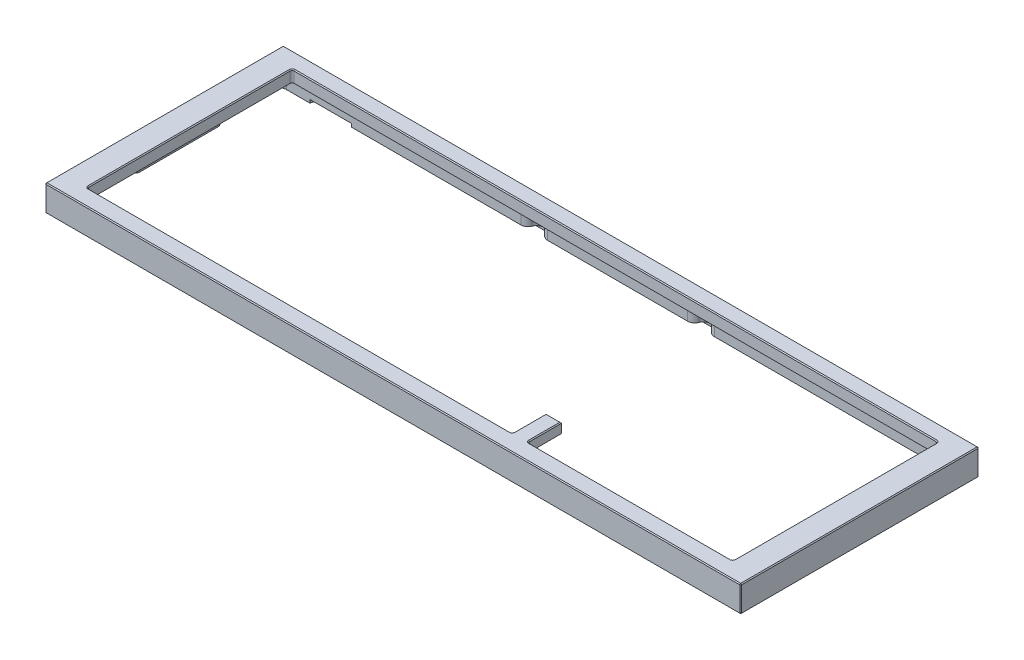
SolidWorks part; units mm, degrees
material "6061 Alloy"
ref_plane "Front Plane" through (0, 0, 0) normal (0, 0, 1) x (1, 0, 0)
ref_plane "Top Plane" through (0, 0, 0) normal (0, 1, 0) x (1, 0, 0)
ref_plane "Right Plane" through (0, 0, 0) normal (1, 0, 0) x (0, 0, -1)
sketch "Sketch1" plane through (0, 0, 0) normal (0, 1, 0) x (1, 0, 0)
  line L1 (0, 0) -> (390.8, 0)
  line L2 (0, 0) -> (0, -133.8)
  line L3 (0, -133.8) -> (390.8, -133.8)
  line L4 (390.8, 0) -> (390.8, -133.8)
  dimension "D1" = 390.8
  dimension "D2" = 133.8
extrude "Boss-Extrude1" add sketch "Sketch1" along normal blind 13.1
sketch "Sketch2" plane through (0, 13.1, 0) normal (0, 1, 0) x (1, 0, 0)
  line L0 (390.8, 0) -> (0, 0) construction
  line L1 (14, -9) -> (376.8, -9)
  line L2 (14, -9) -> (14, -124.3)
  line L3 (14, -124.3) -> (376.8, -124.3)
  line L4 (376.8, -9) -> (376.8, -124.3)
  line L5 (0, -133.8) -> (390.8, -133.8) construction
  line L6 (0, 0) -> (0, -133.8) construction
  line L7 (390.8, -133.8) -> (390.8, 0) construction
  line L8 (390.8, -133.8) -> (390.8, 0) construction
  line L9 (261.6, -124.3) -> (252.9, -124.3)
  line L10 (261.6, -124.3) -> (261.6, -105.25)
  line L11 (261.6, -105.25) -> (252.9, -105.25)
  line L12 (252.9, -124.3) -> (252.9, -105.25)
  line L13 (0, -133.8) -> (390.8, -133.8) construction
  dimension "D1" = 9
  dimension "D2" = 9.5
  dimension "D3" = 14
  dimension "D4" = 14
  dimension "D5" = 129.2
  dimension "D6" = 137.9
  dimension "D7" = 28.55
extrude "Cut-Extrude1" cut sketch "Sketch2" against normal through all contours L3 L12 L11 L10 L4 L1 L2 region at (195.154, 13.1, 66.4586)
sketch "Sketch3" plane through (0, 0, 0) normal (0, -1, 0) x (1, 0, 0)
  line L0 (390.8, 0) -> (0, 0) construction
  line L1 (385.5, 2.6) -> (5.3, 2.6)
  line L2 (385.5, 2.6) -> (385.5, 131.2)
  line L3 (385.5, 131.2) -> (5.3, 131.2)
  line L4 (5.3, 2.6) -> (5.3, 131.2)
  line L5 (390.8, 133.8) -> (390.8, 0) construction
  point P4 (195.4, 2.6)
  point P7 (195.4, 0)
  point P8 (385.5, 66.9)
  point P11 (390.8, 66.9)
  dimension "D1" = 380.2
  dimension "D2" = 128.6
extrude "Cut-Extrude2" cut sketch "Sketch3" against normal blind 6.6 contours L2 L1 L4 L3
sketch "Sketch5" plane through (0, 6.6, 0) normal (0, -1, 0) x (1, 0, 0)
  line L0 (290, 128.2) -> (285, 128.2)
  line L1 (290, 128.2) -> (290, 131.2)
  line L2 (290, 131.2) -> (285, 131.2)
  line L3 (285, 128.2) -> (285, 131.2)
  line L4 (105, 128.2) -> (100, 128.2)
  line L5 (105, 128.2) -> (105, 131.2)
  line L6 (105, 131.2) -> (100, 131.2)
  line L7 (100, 128.2) -> (100, 131.2)
  line L8 (8.3, 45) -> (8.3, 88.8)
  line L9 (382.5, 45) -> (382.5, 88.8)
  line L10 (0, 133.8) -> (390.8, 133.8) construction
  line L11 (5.3, 2.6) -> (5.3, 131.2) construction
  line L12 (390.8, 0) -> (0, 0) construction
  line L13 (385.5, 2.6) -> (385.5, 131.2) construction
  line L15 (385.5, 131.2) -> (5.3, 131.2) construction
  line L16 (385.5, 131.2) -> (5.3, 131.2) construction
  line L17 (385.5, 2.6) -> (5.3, 2.6) construction
  line L18 (5.3, 2.6) -> (5.3, 131.2) construction
  circle A0 centre (102.5, 128.2) radius 2.5
  circle A1 centre (287.5, 128.2) radius 2.5
  circle A2 centre (102.5, 2.6) radius 2.5
  circle A3 centre (195.4, 2.6) radius 2.5
  circle A4 centre (287.5, 2.6) radius 2.5
  circle A5 centre (385.5, 45) radius 3
  circle A6 centre (385.5, 88.8) radius 3
  circle A7 centre (5.3, 45) radius 3
  circle A8 centre (5.3, 88.8) radius 3
  line M9 (5.3, 131.2) -> (5.3, 2.6)
  line M10 (5.3, 2.6) -> (385.5, 2.6)
  line M11 (385.5, 2.6) -> (385.5, 131.2)
  dimension "D1" = 5
  dimension "D5" = 6
  dimension "D2" = 185
  dimension "D3" = 92.9
  dimension "D4" = 185
  dimension "D6" = 45
  dimension "D7" = 97.2
  dimension "D8" = 3
  dimension "D9" = 97.2
  dimension "D10" = 45
  dimension "D11" = 45
extrude "Boss-Extrude2" add sketch "Sketch5" along normal up to surface (6.6 mm away) contours A6 L9 A5 M11 | A5 M11 | A6 M11 | A4 M10 | A3 M10 | A2 M10 | A7 M9 | A8 A7 L8 M9 | A8 M9 | A0 | L7 L6 L5 L4 | L3 L2 L1 L0 | A1 region at (6.8273, 6.6, 66.9) region at (6.5732, 6.6, 45) region at (384.2268, 6.6, 45) region at (287.5, 6.6, 3.661) region at (195.4, 6.6, 3.661) region at (102.5, 6.6, 3.661) region at (6.5732, 6.6, 88.8) region at (383.9727, 6.6, 66.9) region at (384.2268, 6.6, 88.8) up to face at (195.4, 0, 66.9)
sketch "Sketch6" plane through (0, 6.6, 0) normal (0, -1, 0) x (-1, 0, 0)
  line L0 (-195.4, 0) -> (-195.4, -133.8) construction
  line L1 (-390.8, 0) -> (0, 0) construction
  line L2 (0, -133.8) -> (-390.8, -133.8) construction
  line L3 (-390.8, -66.9) -> (0, -66.9) construction
  line L4 (-390.8, -133.8) -> (-390.8, 0) construction
  line L5 (0, 0) -> (0, -133.8) construction
  line L6 (-285, -2.6) -> (-197.9, -2.6) construction
  line L7 (-385.5, -2.6) -> (-385.5, -42) construction
  line L8 (-385.5, -2.6) -> (-385.5, -42) construction
  point P12 (-382.9, -22.7)
  point P13 (-382.9, -111)
  point P14 (-324.8, -129)
  point P15 (-192.2, -129)
  point P16 (-148.6, -5.4)
  point P18 (-64.4, -129)
  point P19 (-7.9, -111)
  point P20 (-7.9, -22.7)
  point P22 (-242.3, -5.4)
  dimension "D1" = 22.8
  dimension "D2" = 22.7
  dimension "D3" = 7.9
  dimension "D4" = 66
  dimension "D5" = 4.8
  dimension "D6" = 198.6
  dimension "D7" = 326.4
  dimension "D8" = 2.8
  dimension "D9" = 143.2
  dimension "D10" = 236.9
sketch "Sketch7" plane through (0, 0, 0) normal (0, -1, 0) x (1, 0, 0)
  arc A0 (382.5, 45) -> (385.5, 42) centre (385.5, 45) ccw construction
  arc A1 (385.5, 91.8) -> (382.5, 88.8) centre (385.5, 88.8) ccw construction
  arc A2 (290, 2.6) -> (285, 2.6) centre (287.5, 2.6) ccw construction
  arc A3 (197.9, 2.6) -> (192.9, 2.6) centre (195.4, 2.6) ccw construction
  arc A4 (105, 2.6) -> (100, 2.6) centre (102.5, 2.6) ccw construction
  arc A5 (5.3, 42) -> (8.3, 45) centre (5.3, 45) ccw construction
  arc A6 (8.3, 88.8) -> (5.3, 91.8) centre (5.3, 88.8) ccw construction
  arc A7 (100, 128.2) -> (105, 128.2) centre (102.5, 128.2) ccw construction
  arc A8 (285, 128.2) -> (290, 128.2) centre (287.5, 128.2) ccw construction
  point P0 (385.5, 45)
  point P1 (385.5, 88.8)
  point P2 (287.5, 128.2)
  point P3 (102.5, 128.2)
  point P4 (5.3, 88.8)
  point P5 (5.3, 45)
  point P6 (102.5, 2.6)
  point P7 (195.4, 2.6)
  point P8 (287.5, 2.6)
sketch "Sketch8" plane through (0, 6.6, 0) normal (0, -1, 0) x (1, 0, 0)
  line L1 (261.6, 105.25) -> (252.9, 105.25)
  line L2 (261.6, 105.25) -> (261.6, 124.3)
  line L3 (261.6, 124.3) -> (252.9, 124.3)
  line L4 (252.9, 105.25) -> (252.9, 124.3)
extrude "Cut-Extrude3" cut sketch "Sketch8" against normal blind 1
hole_wizard "M2x0.4 Tapped Hole2" positions "3DSketch3" profile "Sketch11" tap size "M2x0.4" standard "ANSI Metric"
sketch3d "3DSketch3"
  point P0 (382.9, 6.6, 22.7)
  point P3 (382.9, 6.6, 111)
  point P6 (324.8, 6.6, 129)
  point P9 (192.2, 6.6, 129)
  point P12 (64.4, 6.6, 129)
  point P15 (7.9, 6.6, 22.7)
  point P18 (7.9, 6.6, 111)
  point P22 (242.3, 6.6, 5.4)
  point P25 (148.6, 6.6, 5.4)
sketch "Sketch11" plane through (382.9, 6.6, 22.7) normal (1, 0, 0) x (0, 0, -1)
  line L0 (0, 0) -> (0, 4.4807)
  line L1 (0, 4.4807) -> (0.8, 4)
  line L2 (0.8, 4) -> (0.8, 0)
  line L5 (0.8, 0) -> (0, 0)
  line L10 (0, 4.4807) -> (-0.8, 4) construction
  line L11 (0, -6.35) -> (0, 107.95) construction
  dimension "Tap Drill Dia." = 1.6
  dimension "Tap Drill Depth" = 4
  dimension "Drill Angle" = 118
cosmetic thread "Hole Thread10" parameters "D1"=4, "D2"=2
cosmetic thread "Hole Thread11" parameters "D1"=4, "D2"=2
cosmetic thread "Hole Thread12" parameters "D1"=4, "D2"=2
cosmetic thread "Hole Thread13" parameters "D1"=4, "D2"=2
cosmetic thread "Hole Thread14" parameters "D1"=4, "D2"=2
cosmetic thread "Hole Thread15" parameters "D1"=4, "D2"=2
cosmetic thread "Hole Thread16" parameters "D1"=4, "D2"=2
cosmetic thread "Hole Thread17" parameters "D1"=4, "D2"=2
cosmetic thread "Hole Thread18" parameters "D1"=4, "D2"=2
fillet "Fillet1" radius 4 12 edges at (385.5, 3.3, 42) (385.5, 3.3, 2.6) (5.3, 3.3, 2.6) (5.3, 3.3, 42) (5.3, 3.3, 91.8) (5.3, 3.3, 131.2) (100, 3.3, 131.2) (105, 3.3, 131.2) (290, 3.3, 131.2) (285, 3.3, 131.2) (385.5, 3.3, 131.2) (385.5, 3.3, 91.8)
fillet "Fillet2" radius 1.1 12 edges at (376.8, 9.85, 9) (376.8, 9.85, 124.3) (14, 9.85, 124.3) (14, 9.85, 9) (105, 3.3, 2.6) (100, 3.3, 2.6) (197.9, 3.3, 2.6) (192.9, 3.3, 2.6) (285, 3.3, 2.6) (290, 3.3, 2.6) (261.6, 10.35, 124.3) (252.9, 10.35, 124.3)
sketch "Sketch14" plane through (0, 0, 0) normal (0, -1, 0) x (1, 0, 0)
  line L0 (390.8, 0) -> (0, 0) construction
  line L1 (388.8, 0) -> (2, 0)
  line L2 (388.8, 0) -> (388.8, 131.8)
  line L3 (388.8, 131.8) -> (2, 131.8)
  line L4 (2, 0) -> (2, 131.8)
  line L5 (0, 0) -> (0, 133.8) construction
  line L6 (390.8, 133.8) -> (390.8, 0) construction
  line L7 (0, 133.8) -> (390.8, 133.8) construction
  line L9 (390.8, 0) -> (0, 0)
  line L10 (390.8, 0) -> (390.8, 133.8)
  line L11 (390.8, 133.8) -> (0, 133.8)
  line L12 (0, 0) -> (0, 133.8)
  line L13 (390.8, 0) -> (0, 0)
  line L14 (390.8, 0) -> (390.8, 2)
  line L15 (390.8, 2) -> (0, 2)
  line L16 (0, 0) -> (0, 2)
  line M21 (0, 0) -> (390.8, 0)
  line M22 (390.8, 0) -> (390.8, 133.8)
  line M25 (0, 0) -> (390.8, 0)
  dimension "D1" = 2
  dimension "D2" = 2
  dimension "D3" = 2
  dimension "D4" = 2
extrude "Boss-Extrude3" add sketch "Sketch14" along normal blind 1.7 contours L12 L9 L4 L3 L2 L10 L11 | L2 L15 L4 M25 M21 | L15 L2 M22 M21 | L4 L15 L12 M25 region at (195.4, 0, 1) region at (389.8, 0, 1) region at (1, 0, 1) region at (389.2124, 0, 66.9)
sketch "Sketch16" plane through (0, 6.6, 0) normal (0, -1, 0) x (1, 0, 0)
  line L0 (5.3, 6.6) -> (5.3, 39.2554) construction
  line L1 (385.5, 2.6) -> (5.3, 2.6)
  line L2 (385.5, 2.6) -> (385.5, 7.6)
  line L3 (385.5, 7.6) -> (5.3, 7.6)
  line L4 (5.3, 2.6) -> (5.3, 7.6)
  line L5 (385.5, 6.6) -> (385.5, 39.2554) construction
  line L6 (381.5, 2.6) -> (290.9278, 2.6) construction
  line L7 (246.3, 6.4) -> (246.3, 7.6)
  line L8 (238.3, 6.4) -> (238.3, 7.6)
  line L9 (152.6, 6.4) -> (152.6, 7.6)
  line L10 (144.6, 6.4) -> (144.6, 7.6)
  circle A0 centre (242.3, 6.4) radius 4
  circle A1 centre (148.6, 6.4) radius 4
  point P24 (242.3, 5.4)
  point P26 (148.6, 5.4)
  dimension "D2" = 8
  dimension "D1" = 5
  dimension "D3" = 1.2
  dimension "D4" = 1.2
extrude "Boss-Extrude4" add sketch "Sketch16" along normal up to surface (6.6 mm away) contours A0 L1 L2 L3 L7 | A1 L1 A0 L8 L3 L9 | A1 L10 L3 L4 L1 region at (315.6181, 6.6, 5.0935) region at (195.45, 6.6, 5.079) region at (75.2319, 6.6, 5.0935) up to face at (195.4, 0, 66.9)
sketch "Sketch17" plane through (0, 6.6, 0) normal (0, -1, 0) x (1, 0, 0)
  circle A0 centre (148.6, 6.4) radius 4
  circle A1 centre (242.3, 6.4) radius 4
  arc A2 (149.849, 2.6) -> (152.6, 6.4) centre (148.6, 6.4) ccw construction
  dimension "D1" = 8
  dimension "D2" = 1
extrude "Cut-Extrude5" cut sketch "Sketch17" along normal up to surface (6.6 mm away) up to face at (195.3316, 0, 64.1007)
sketch "Sketch18" plane through (0, 0, 0) normal (0, 0, -1) x (-1, 0, 0)
  line L0 (0, -1.7) -> (-390.8, -1.7) construction
  line L1 (-40.3, -1.7) -> (-28.3, -1.7)
  line L2 (-40.3, -1.7) -> (-40.3, 1.8)
  line L3 (-40.3, 1.8) -> (-28.3, 1.8)
  line L4 (-28.3, -1.7) -> (-28.3, 1.8)
  line L5 (0, 13.1) -> (0, -1.7) construction
  point P6 (-34.3, 1.8)
  dimension "D1" = 12
  dimension "D2" = 3.5
  dimension "D3" = 34.3
extrude "Cut-Extrude6" cut sketch "Sketch18" against normal blind 10
fillet "Fillet4" radius 4 4 edges at (144.6, 3.3, 7.6) (152.6, 3.3, 7.6) (238.3, 3.3, 7.6) (246.3, 3.3, 7.6)
hole_wizard "M2x0.4 Tapped Hole3" positions "3DSketch2" profile "Sketch10" tap size "M2x0.4" standard "ANSI Metric"
sketch3d "3DSketch2"
  line L0 (390.8, -1.7, 0) -> (390.8, -1.7, 133.8) construction
  line L1 (0, -1.7, 133.8) -> (0, -1.7, 0) construction
  line L7 (388.8, 0, 2) -> (40.3, 0, 2) construction
  point P0 (385.5, 0, 45)
  point P3 (385.5, 0, 88.8)
  point P6 (287.5, 0, 128.2)
  point P9 (102.5, 0, 128.2)
  point P12 (5.3, 0, 88.8)
  point P15 (5.3, 0, 45)
  point P30 (312.8185, 0, 4.3)
  point P32 (195.4074, 0, 4.3)
  point P34 (77.9815, 0, 4.3)
  dimension "D1" = 78
  dimension "D2" = 78
  dimension "D3" = 195.4
  dimension "D4" = 2.3
sketch "Sketch10" plane through (385.5, 0, 45) normal (1, 0, 0) x (0, 0, -1)
  line L0 (0, 0) -> (0, 4.4807)
  line L1 (0, 4.4807) -> (0.8, 4)
  line L2 (0.8, 4) -> (0.8, 0)
  line L5 (0.8, 0) -> (0, 0)
  line L10 (0, 4.4807) -> (-0.8, 4) construction
  line L11 (0, -6.35) -> (0, 107.95) construction
  dimension "Tap Drill Dia." = 1.6
  dimension "Tap Drill Depth" = 4
  dimension "Drill Angle" = 118
cosmetic thread "Hole Thread4" parameters "D1"=4, "D2"=2
cosmetic thread "Hole Thread5" parameters "D1"=4, "D2"=2
cosmetic thread "Hole Thread6" parameters "D1"=4, "D2"=2
cosmetic thread "Hole Thread7" parameters "D1"=4, "D2"=2
cosmetic thread "Hole Thread8" parameters "D1"=4, "D2"=2
cosmetic thread "Hole Thread9" parameters "D1"=4, "D2"=2
cosmetic thread "Hole Thread19" parameters "D1"=4, "D2"=2
cosmetic thread "Hole Thread20" parameters "D1"=4, "D2"=2
cosmetic thread "Hole Thread21" parameters "D1"=4, "D2"=2
fillet "Fillet5" radius 4 6 edges at (5.3, 3.3, 7.6) (385.5, 3.3, 7.6) (388.8, -0.85, 2) (388.8, -0.85, 131.8) (2, -0.85, 131.8) (2, -0.85, 2)
sketch "Sketch20" plane through (0, 0, 0) normal (0, -1, 0) x (1, 0, 0)
  line L2 (40.3, 2) -> (40.3, 7.6)
  line L3 (40.3, 7.6) -> (45.9, 7.6)
  line L4 (28.3, 2) -> (28.3, 7.6)
  line L5 (28.3, 7.6) -> (22.7, 7.6)
  line L6 (384.8, 2) -> (40.3, 2) construction
  circle A0 centre (40.3, 7.6) radius 5.6
  circle A1 centre (28.3, 7.6) radius 5.6
extrude "Cut-Extrude7" cut sketch "Sketch20" against normal up to surface (1.8 mm away) contours L2 A0 L3 | L5 A1 L4 region at (42.6767, 0, 5.2233) region at (25.9233, 0, 5.2233) up to face at (34.3, 1.8, 3.8)
chamfer "Chamfer1" distance 0.5 angle 45 27 edges at (14.15, -1.7, 0) (0, -1.7, 66.9) (195.4, -1.7, 133.8) (390.8, -1.7, 66.9) (215.55, -1.7, 0) (195.4, 13.1, 0) (390.8, 13.1, 66.9) (195.4, 13.1, 133.8) (0, 13.1, 66.9) (252.5778, 13.1, 123.9778) (252.9, 13.1, 114.225) (257.25, 13.1, 105.25) (261.6, 13.1, 114.225) (261.9222, 13.1, 123.9778) (319.2, 13.1, 124.3) (376.4778, 13.1, 123.9778) (376.8, 13.1, 66.65) (376.4778, 13.1, 9.3222) (195.4, 13.1, 9) (14.3222, 13.1, 9.3222) (14, 13.1, 66.65) (14.3222, 13.1, 123.9778) (133.45, 13.1, 124.3) (0, 5.7, 0) (0, 5.7, 133.8) (390.8, 5.7, 133.8) (390.8, 5.7, 0)
